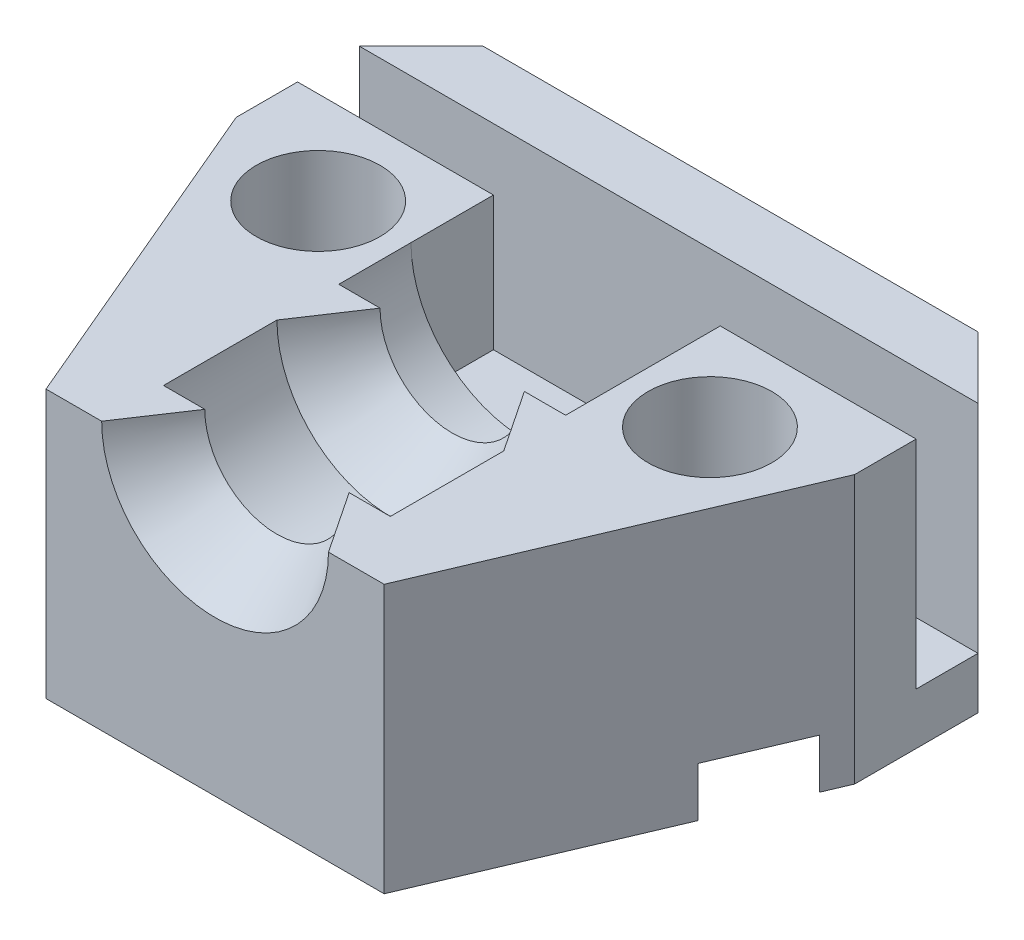
SolidWorks part; units mm, degrees
ref_plane "Front Plane" through (0, 0, 0) normal (0, 0, 1) x (1, 0, 0)
ref_plane "Top Plane" through (0, 0, 0) normal (0, 1, 0) x (1, 0, 0)
ref_plane "Right Plane" through (0, 0, 0) normal (1, 0, 0) x (0, 0, -1)
sketch "Sketch1" plane through (0, 0, 0) normal (0, 1, 0) x (1, 0, 0)
  line L1 (-7.5, 6.25) -> (7.5, 6.25)
  line L2 (-7.5, 6.25) -> (-7.5, -6.25)
  line L3 (-7.5, -6.25) -> (7.5, -6.25)
  line L4 (7.5, 6.25) -> (7.5, -6.25)
  line L5 (-7.5, 6.25) -> (7.5, -6.25) construction
  line L6 (-7.5, -6.25) -> (7.5, 6.25) construction
  point P0 (0, 0)
  dimension "D1" = 15
  dimension "D2" = 12.5
extrude "Boss-Extrude1" add sketch "Sketch1" along normal blind 6.5
sketch "Sketch2" plane through (0, 0, 0) normal (0, 1, 0) x (1, 0, 0)
  line L0 (7.5, -6.25) -> (7.5, 6.25) construction
  line L1 (-7.5, 6.25) -> (-7.5, -6.25) construction
  line L2 (7.5, 6.25) -> (-7.5, 6.25) construction
  circle A1 centre (4.75, 1) radius 1.5
  circle A2 centre (-4.75, 1) radius 1.5
  circle A3 centre (4.75, 1) radius 2.5
  circle A4 centre (-4.75, 1) radius 2.5
  dimension "D1" = 3
  dimension "D2" = 3
  dimension "D6" = 5
  dimension "D7" = 5
  dimension "D3" = 2.75
  dimension "D4" = 2.75
  dimension "D5" = 5.25
extrude "Cut-Extrude1" cut sketch "Sketch2" along normal through all contours A1 | A2
chamfer "Chamfer1" distance 3.4 angle 67 2 edges at (-7.5, 3.25, 6.25) (7.5, 3.25, 6.25) first distance on face at (0, 3.25, 6.25)
sketch "Sketch3" plane through (0, 6.5, 0) normal (0, 1, 0) x (1, 0, 0)
  line L0 (-7.5, 4.75) -> (7.5, 4.75)
  line L1 (-7.5, 6.25) -> (-7.5, 1.7599) construction
  line L2 (7.5, 1.7599) -> (7.5, 6.25) construction
  line L3 (7.5, 4.75) -> (7.5, 3.25)
  line L4 (7.5, 3.25) -> (2.75, 3.25)
  line L5 (2.75, 3.25) -> (2.75, 1.25)
  line L6 (2.75, 1.25) -> (-2.75, 1.25)
  line L7 (-2.75, 1.25) -> (-2.75, 3.25)
  line L8 (-2.75, 3.25) -> (-7.5, 3.25)
  line L9 (-7.5, 3.25) -> (-7.5, 4.75)
  line L10 (7.5, 6.25) -> (-7.5, 6.25) construction
  line L11 (-2.75, 3.25) -> (2.75, 3.25)
  line M11 (7.5, 1.7599) -> (7.5, 6.25)
  line M13 (-7.5, 6.25) -> (-7.5, 1.7599)
  dimension "D1" = 5.5
  dimension "D2" = 2
  dimension "D3" = 1.5
  dimension "D4" = 1.5
extrude "Cut-Extrude5" cut sketch "Sketch2<3>" along normal blind 1.2
sketch "Sketch2<3>" plane through (0, 0, 0) normal (0, 1, 0) x (1, 0, 0) same geometry as "Sketch2"
extrude "Cut-Extrude4" cut sketch "Sketch3<3>" against normal blind 5.25 contours L8 L11 L4 L0 M11 M13 region at (0, 6.5, -4)
sketch "Sketch3<3>" plane through (0, 6.5, 0) normal (0, 1, 0) x (1, 0, 0) same geometry as "Sketch3"
sketch "Sketch4" plane through (0, 6.5, 0) normal (0, 1, 0) x (1, 0, 0)
  line L0 (2.75, 1.25) -> (2.75, -0.5)
  line L1 (2.75, -0.5) -> (1.75, -0.5)
  line L2 (1.75, -0.5) -> (2.75, -2)
  line L3 (2.75, -2) -> (2.75, -4.75)
  line L4 (2.75, -4.75) -> (1.75, -4.75)
  line L5 (1.75, -4.75) -> (2.75, -6.25)
  line L6 (-4.1, -6.25) -> (4.1, -6.25) construction
  line L7 (2.75, -6.25) -> (0, -6.25)
  line L11 (0, -6.25) -> (0, 1.25)
  line L12 (0, 1.25) -> (2.75, 1.25)
  dimension "D1" = 1
  dimension "D2" = 1.75
  dimension "D3" = 1.5
  dimension "D4" = 1.5
  dimension "D5" = 2.75
  dimension "D6" = 7.5
revolve "Cut-Revolve1" cut sketch "Sketch4" angle 360 about L11
extrude "Cut-Extrude3" cut sketch "Sketch3" against normal blind 3.25 contours L11 L7 L6 L5 region at (0, 6.5, -2.25)
chamfer "Chamfer2" distance 1.5 angle 45 2 edges at (-7.5, 3.25, -6.25) (7.5, 3.25, -6.25)
